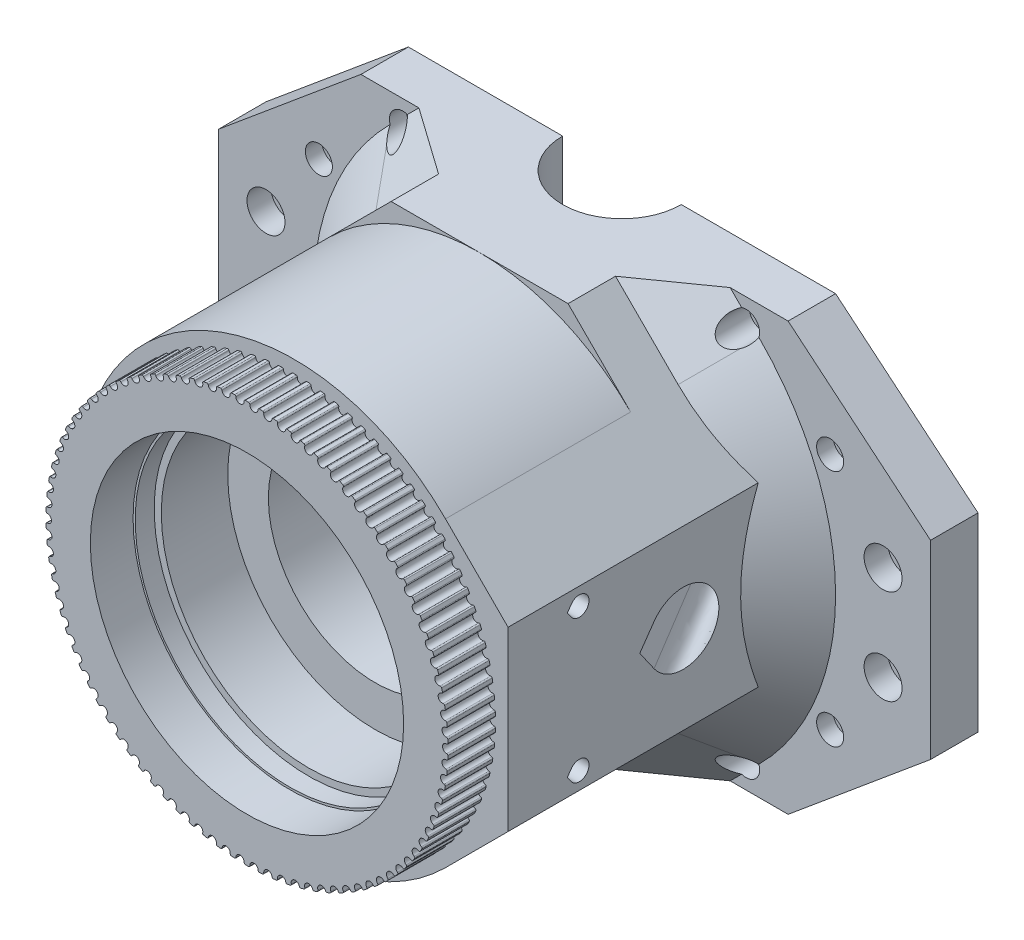
SolidWorks part; units mm, degrees
ref_plane "Front Plane" through (0, 0, 0) normal (1, 0, 0) x (0, 1, 0)
ref_plane "Top Plane" through (0, 0, 0) normal (0, 0, 1) x (0, 1, 0)
ref_plane "Right Plane" through (0, 0, 0) normal (0, 1, 0) x (-1, 0, 0)
sketch "Sketch1" plane through (0, 0, 0) normal (1, 0, 0) x (0, 1, 0)
  line L0 (-45, -80) -> (45, -80)
  line L1 (-31, 0) -> (31, 0)
  line L2 (-31, 0) -> (-31, -14)
  line L3 (-31, -14) -> (31, -14)
  line L4 (31, 0) -> (31, -14)
  line L5 (-31, 0) -> (31, -14) construction
  line L6 (-31, -14) -> (31, 0) construction
  line L7 (-31, -36) -> (31, -36)
  line L8 (-31, -36) -> (-31, -50)
  line L9 (-31, -50) -> (31, -50)
  line L10 (31, -36) -> (31, -50)
  line L11 (-31, -36) -> (31, -50) construction
  line L12 (-31, -50) -> (31, -36) construction
  line L13 (45, -80) -> (45, -1)
  line L14 (45, -1) -> (31, -1)
  line L15 (-31, -1) -> (-45, -1)
  line L16 (-45, -1) -> (-45, -80)
  point P0 (0, -7)
  point P5 (0, -43)
  point P16 (0, 0)
  dimension "D1" = 62
  dimension "D2" = 62
  dimension "D3" = 14
  dimension "D4" = 14
  dimension "D5" = 30
  dimension "D6" = 1
  dimension "D7" = 22
  dimension "D8" = 90
sketch "Sketch2" plane through (0, 0, 0) normal (0, 0, 1) x (0, 1, 0)
  line L0 (-45, 45) -> (-20, 75)
  line L1 (-20, 75) -> (20, 75)
  line L2 (45, 45) -> (-45, 45)
  line L3 (45, 45) -> (45, -45)
  line L4 (45, -45) -> (-45, -45)
  line L5 (-45, 45) -> (-45, -45)
  line L6 (45, 45) -> (-45, -45) construction
  line L7 (45, -45) -> (-45, 45) construction
  line L8 (20, 75) -> (45, 45)
  line L9 (-45, -45) -> (-20, -75)
  line L10 (-20, -75) -> (20, -75)
  line L11 (20, -75) -> (45, -45)
  line L12 (0, 75) -> (0, -75) construction
  line L13 (-45, -18.6396) -> (-18.6396, -45)
  line L14 (-18.6396, 45) -> (-45, 18.6396)
  line L15 (45, 18.6396) -> (18.6396, 45)
  line L16 (18.6396, -45) -> (45, -18.6396)
  circle A0 centre (0, 0) radius 45
  circle A1 centre (0, 0) radius 31.05
  circle A2 centre (0, 0) radius 22.5
  point P15 (0, 0)
  point P27 (0, 0)
  dimension "D1" = 90
  dimension "D2" = 62.1
  dimension "D3" = 45
  dimension "D4" = 150
  dimension "D5" = 40
  dimension "D6" = 4
  dimension "D7" = 45
extrude "Boss-Extrude1" add sketch "Sketch2" against normal up to vertex (80 mm away) from offset 11 contours A0 A1 | A1 A2 region at (-40.3987, 16.7337, 0) region at (0, -30.1718, 0) up to point (0, -45, -80) offset against normal yes
extrude "Boss-Extrude2" add sketch "Sketch2<3>" along normal blind 10 from surface contours A0 L5 L4 | A0 L2 L5 | A0 L4 L3 | A0 L3 L2 | L10 L11 L4 L9 | L8 L1 L0 L2 | A0 L13 L4 | A0 L5 L13 | A0 L4 | A0 L3 | A0 L2 L14 | A0 L14 L5 | A0 L3 L15 | A0 L15 L2 region at (-58.0769, 0, 0) region at (-36.2132, -36.2132, 0) region at (-42.2926, -17.5182, 0) region at (-17.5182, -42.2926, 0) region at (-42.2926, 17.5182, 0) region at (17.5182, -42.2926, 0) region at (-36.2132, 36.2132, 0) region at (-17.5182, 42.2926, 0) region at (36.2132, -36.2132, 0) region at (42.2926, -17.5182, 0) region at (17.5182, 42.2926, 0) region at (58.0769, 0, 0) region at (42.2926, 17.5182, 0) region at (36.2132, 36.2132, 0) starting at face at (45, 0, -80)
sketch "Sketch2<3>" plane through (0, 0, 0) normal (0, 0, 1) x (0, 1, 0) same geometry as "Sketch2"
extrude "Boss-Extrude4" add sketch "Sketch2<6>" along normal blind 20 from surface contours A0 L5 | A0 L5 L13 | A0 L16 L3 | A0 L3 L15 region at (-17.5182, -42.2926, 0) region at (17.5182, -42.2926, 0) region at (-17.5182, 42.2926, 0) region at (17.5182, 42.2926, 0) starting at face at (-47.5, 0, -70)
sketch "Sketch2<6>" plane through (0, 0, 0) normal (0, 0, 1) x (0, 1, 0) same geometry as "Sketch2"
sketch "Sketch5" plane through (0, -45, 0) normal (0, -1, 0) x (1, 0, 0)
  line L0 (-45, -80) -> (45, -80) construction
  circle A0 centre (0, -80) radius 12.5
  line M9 (-45, -80) -> (45, -80)
  dimension "D1" = 25
extrude "Cut-Extrude3" cut sketch "Sketch5" against normal through all contours A0 M9 region at (0, -45, -74.6948)
sketch "Sketch6" plane through (0, 0, -70) normal (0, 0, 1) x (1, 0, 0)
  line L0 (-65, 10) -> (-65, -10) construction
  line L1 (0, 0) -> (-99.7082, 0) construction
  line L2 (65, 10) -> (65, -10) construction
  line L3 (75, -20) -> (75, 20) construction
  line L4 (-75, -20) -> (-75, 20) construction
  circle A0 centre (65, 10) radius 4
  circle A1 centre (65, 10) radius 2.05
  circle A2 centre (-65, 10) radius 2.05
  circle A3 centre (-65, 10) radius 4
  circle A4 centre (-65, -10) radius 2.05
  circle A5 centre (-65, -10) radius 4
  circle A6 centre (65, -10) radius 2.05
  circle A7 centre (65, -10) radius 4
  point P3 (-65, 0)
  point P9 (65, 0)
  dimension "D4" = 8
  dimension "D5" = 4.1
  dimension "D1" = 20
  dimension "D2" = 10
  dimension "D3" = 10
  dimension "D6" = 2
  dimension "D7" = 2
extrude "Cut-Extrude4" cut sketch "Sketch6" against normal through all contours A1 | A4 | A2 | A6
extrude "Cut-Extrude5" cut sketch "Sketch6<4>" against normal blind 5
sketch "Sketch6<4>" plane through (0, 0, -70) normal (0, 0, 1) x (1, 0, 0) same geometry as "Sketch6"
extrude "Cut-Extrude1" cut sketch "Sketch2<4>" against normal blind 28 contours A1
sketch "Sketch2<4>" plane through (0, 0, 0) normal (0, 0, 1) x (0, 1, 0) same geometry as "Sketch2"
extrude "Cut-Extrude2" cut sketch "Sketch2<5>" along normal offset from surface (32 mm away) 20 from surface contours A1 up to face at (31.05, 0, -28) starting at face at (67.05, -10, -80)
sketch "Sketch2<5>" plane through (0, 0, 0) normal (0, 0, 1) x (0, 1, 0) same geometry as "Sketch2"
sketch "Sketch7" plane through (0, 0, -70) normal (0, 0, 1) x (1, 0, 0)
  line L0 (-75, 20) -> (75, 20) construction
  line L1 (-45, 45) -> (-18.6396, 45) construction
  line L2 (-45, 45) -> (0, 45) construction
  line L3 (-30, 45) -> (-60, 20) construction
  line L4 (-75, 20) -> (-45, 45) construction
  line L5 (0, 13.0372) -> (0, -13.0372) construction
  line L6 (-13.0372, 0) -> (13.0372, 0) construction
  line L7 (30, 45) -> (60, 20) construction
  line L8 (30, -45) -> (60, -20) construction
  line L9 (-30, -45) -> (-60, -20) construction
  circle A0 centre (-53.8542, 25.1215) radius 1.6
  circle A1 centre (-53.8542, 25.1215) radius 2.85
  circle A2 centre (-36.1458, 39.8785) radius 2.85
  circle A3 centre (-36.1458, 39.8785) radius 1.6
  circle A4 centre (36.1458, 39.8785) radius 1.6
  circle A5 centre (36.1458, 39.8785) radius 2.85
  circle A6 centre (53.8542, 25.1215) radius 2.85
  circle A7 centre (53.8542, 25.1215) radius 1.6
  circle A8 centre (53.8542, -25.1215) radius 1.6
  circle A9 centre (53.8542, -25.1215) radius 2.85
  circle A10 centre (36.1458, -39.8785) radius 2.85
  circle A11 centre (36.1458, -39.8785) radius 1.6
  circle A12 centre (-36.1458, -39.8785) radius 1.6
  circle A13 centre (-36.1458, -39.8785) radius 2.85
  circle A14 centre (-53.8542, -25.1215) radius 2.85
  circle A15 centre (-53.8542, -25.1215) radius 1.6
  circle A16 centre (-36.1458, -39.8785) radius 5.5
  circle A17 centre (36.1458, -39.8785) radius 5.5
  point P23 (0, 0)
  point P26 (0, 0)
  dimension "D2" = 5.7
  dimension "D3" = 3.2
  dimension "D6" = 3.2
  dimension "D7" = 5.7
  dimension "D8" = 11
  dimension "D9" = 11
  dimension "D1" = 15
  dimension "D4" = 8
  dimension "D5" = 8
extrude "Cut-Extrude6" cut sketch "Sketch7" against normal through all contours A15 | A0 | A3 | A4 | A7 | A8 | A11 | A12
extrude "Cut-Extrude7" cut sketch "Sketch7<3>" against normal blind 3.5 contours A14 | A1 | A2 | A5 | A6 | A9 | A10 | A13
sketch "Sketch7<3>" plane through (0, 0, -70) normal (0, 0, 1) x (1, 0, 0) same geometry as "Sketch7"
chamfer "Chamfer2" distance 10 angle 45 6 edges at (25.2297, -38.4099, -70) (25.2297, 38.4099, -70) (45, 0, -70) (-25.2297, 38.4099, -70) (-25.2297, -38.4099, -70) (-45, 0, -70)
extrude "Boss-Extrude6" add sketch "Sketch2<7>" against normal up to surface (70 mm away) from surface contours A0 L13 L4 | A0 L4 L16 region at (42.2926, -17.5182, 0) region at (42.2926, 17.5182, 0) up to face at (56.7042, -25.1215, -70) starting at face at (31.05, 0, -11)
sketch "Sketch2<7>" plane through (0, 0, 0) normal (0, 0, 1) x (0, 1, 0) same geometry as "Sketch2"
sketch "Sketch8" plane through (45, 0, 0) normal (1, 0, 0) x (0, 1, 0)
  line L0 (-15, -26) -> (-9.9, -26) construction
  line L1 (15, -26) -> (20.2, -26) construction
  line L2 (-15, -26) -> (-20.2, -26) construction
  line L3 (-9.9, -26) -> (15, -26) construction
  line L4 (-9.9, -26) -> (-9.9, -11) construction
  line L5 (18.6396, -11) -> (-18.6396, -11) construction
  line L6 (-20.2, -26) -> (-20.2, -11)
  line L7 (-31.8198, -11) -> (-18.6396, -11) construction
  line L8 (20.2, -26) -> (20.2, -11)
  line L9 (18.6396, -11) -> (31.8198, -11) construction
  line L10 (-14.0823, -24.6894) -> (-15, -24.0468)
  line L11 (-16.1758, -24.3207) -> (-15, -23.4974)
  line L12 (-15.9177, -24.6894) -> (-15, -24.0468)
  line L13 (-13.8242, -24.3207) -> (-15, -23.4974)
  line L14 (-15, -26) -> (-15, -23.4974) construction
  line L15 (16.1758, -24.3207) -> (15, -23.4974)
  line L16 (15, -26) -> (15, -23.4974) construction
  line L17 (14.0823, -24.6894) -> (15, -24.0468)
  line L18 (13.8242, -24.3207) -> (15, -23.4974)
  line L19 (15.9177, -24.6894) -> (15, -24.0468)
  line L20 (-20.2, -11) -> (20.2, -11)
  line L21 (-20.2, -26) -> (-20.2, -32.9)
  line L22 (20.2, -26) -> (20.2, -32.9)
  line L23 (-20.2, -32.9) -> (20.2, -32.9)
  line L24 (0, -47.9) -> (0, -38.7442) construction
  line L25 (-4.3018, -41.7564) -> (0, -38.7442)
  line L26 (4.3018, -41.7564) -> (0, -38.7442)
  arc A0 (-16.1758, -24.3207) -> (-13.8242, -24.3207) centre (-15, -26) ccw
  arc A1 (-15.9177, -24.6894) -> (-14.0823, -24.6894) centre (-15, -26) ccw
  arc A2 (14.0823, -24.6894) -> (15.9177, -24.6894) centre (15, -26) ccw
  arc A3 (13.8242, -24.3207) -> (16.1758, -24.3207) centre (15, -26) ccw
  arc A4 (-4.3018, -41.7564) -> (4.3018, -41.7564) centre (0, -47.9) ccw
  point P29 (0, -11)
  dimension "D6" = 3.2
  dimension "D7" = 4.1
  dimension "D10" = 3.2
  dimension "D11" = 4.1
  dimension "D15" = 15
  dimension "D1" = 15
  dimension "D2" = 24.9
  dimension "D3" = 5.2
  dimension "D4" = 5.1
  dimension "D5" = 5.2
  dimension "D8" = 55
  dimension "D9" = 55
  dimension "D12" = 55
  dimension "D13" = 55
  dimension "D14" = 6.9
  dimension "D16" = 15
  dimension "D17" = 55
sketch "Sketch3" plane through (0, 0, -11) normal (0, 0, 1) x (1, 0, 0)
  line L0 (0, 0) -> (0, 42.3568)
  line L1 (0, 0) -> (1.4374, 41.1617) construction
  line L2 (0, 0) -> (2.9547, 42.2537)
  line L3 (1.4374, 41.1617) -> (1.4678, 42.0312) construction
  arc A0 (0.6589, 42.3517) -> (2.297, 42.2945) centre (1.4678, 42.0312) ccw
  arc A1 (0, 42.3568) -> (0.6589, 42.3517) centre (0, 0) cw
  arc A2 (2.297, 42.2945) -> (2.9547, 42.2537) centre (0, 0) cw
  arc A3 (0, 31.05) -> (2.1659, 30.9744) centre (0, 0) cw
  circle A4 centre (0, 0) radius 31.05 construction
  circle M5 centre (0, 0) radius 31.05
  dimension "D1" = 42.3568
  dimension "D2" = 2
  dimension "D3" = 2
  dimension "D4" = 42.3568
  dimension "D5" = 41.1868
  dimension "D6" = 0.87
extrude "Boss-Extrude3" add sketch "Sketch3" along normal up to vertex (10 mm away) contours A2 A0 A1 L0 L2 M5 region at (1.2803, 36.6619, -11) up to point (0, 45, -1)
fillet "Fillet1" radius 0.26 2 edges at (2.297, 42.2945, -6) (0.6589, 42.3517, -6)
pattern_circular "CirPattern1" count 90 over 360 about axis through (0, 0, -80) along (0, 0, 1) of "Fillet1", "Boss-Extrude3" reverse direction yes
extrude "Cut-Extrude9" cut sketch "Sketch8" against normal blind 7 contours A0 L13 L11 | A3 L15 L18
extrude "Cut-Extrude10" cut sketch "Sketch8<3>" against normal blind 3 from surface contours A1 L10 L12 | A2 L19 L17 starting at face at (38, -15, -25.2894)
sketch "Sketch8<3>" plane through (45, 0, 0) normal (1, 0, 0) x (0, 1, 0) same geometry as "Sketch8"
sketch "Sketch13" plane through (0, 45, 0) normal (0, 1, 0) x (-1, 0, 0)
  line L6 (-31.05, -48) -> (31.05, -48) construction
  line L7 (-31.05, -48) -> (31.05, -48)
  line L8 (-31.05, -48) -> (-31.05, -62)
  line L9 (-45, -38.7442) -> (-31.05, -62)
  dimension "D1" = 14
extrude "Cut-Extrude11" cut sketch "Sketch8<4>" along direction (-0.5144, 0, -0.8575) on the side against the normal blind 45 contours A4 L26 L25
sketch "Sketch8<4>" plane through (45, 0, 0) normal (1, 0, 0) x (0, 1, 0) same geometry as "Sketch8"
sketch "Sketch12" plane through (0, 0, -1) normal (0, 0, 1) x (1, 0, 0)
  circle A0 centre (0, 0) radius 32.55
  circle A1 centre (0, 0) radius 33
  dimension "D1" = 65.1
  dimension "D2" = 66
extrude "Cut-Extrude13" cut sketch "Sketch12" against normal blind 13 contours A0
extrude "Cut-Extrude14" cut sketch "Sketch12<3>" against normal blind 9 contours A1
sketch "Sketch12<3>" plane through (0, 0, -1) normal (0, 0, 1) x (1, 0, 0) same geometry as "Sketch12"
equation "\"D1@Sketch3\"=3 * 90 / PI / 2-0.615"
equation "\"D3@Sketch3\"=\"D2@Sketch3\""
equation "\"D4@Sketch3\"=\"D1@Sketch3\""
equation "\"D5@Sketch3\"=\"D1@Sketch3\"-1.17"
